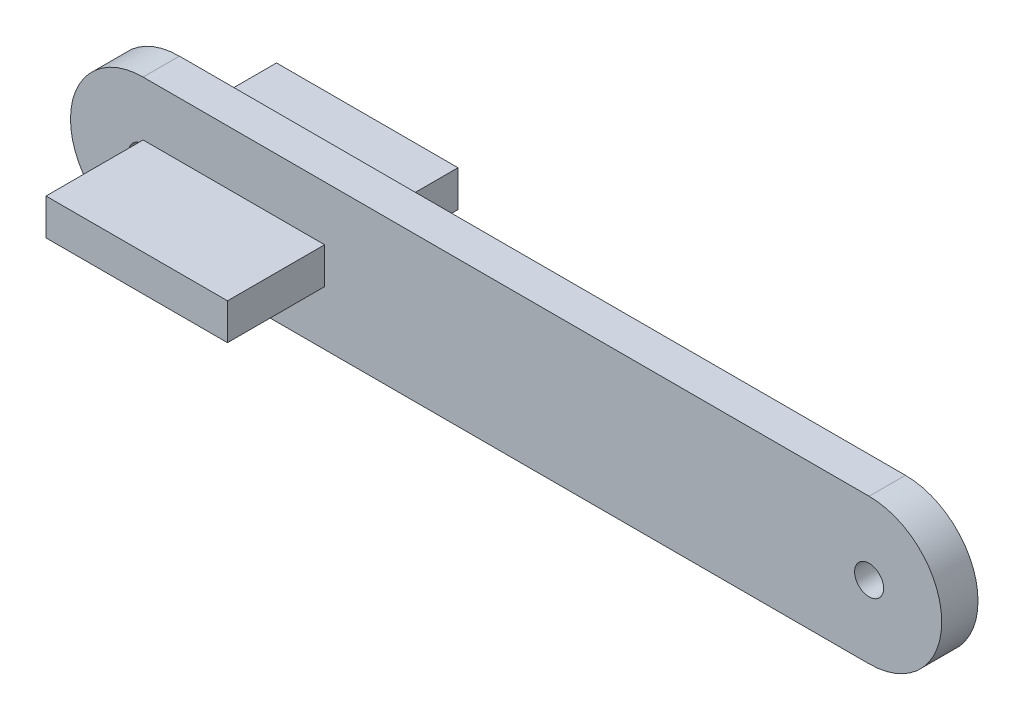
SolidWorks part; units mm, degrees
ref_plane "Front Plane" through (0, 0, 0) normal (0, 0, 1) x (1, 0, 0)
ref_plane "Top Plane" through (0, 0, 0) normal (0, 1, 0) x (1, 0, 0)
ref_plane "Right Plane" through (0, 0, 0) normal (1, 0, 0) x (0, 0, -1)
sketch "Sketch1" plane through (0, 0, 0) normal (0, 0, 1) x (1, 0, 0)
  line L0 (-50, 0) -> (50, 0) construction
  line L1 (-50, 10) -> (50, 10)
  line L2 (-50, -10) -> (50, -10)
  arc A0 (-50, 10) -> (-50, -10) centre (-50, 0) ccw
  arc A1 (50, -10) -> (50, 10) centre (50, 0) ccw
  circle A2 centre (-50, 0) radius 2
  circle A3 centre (50, 0) radius 2
  point P2 (0, 0)
  dimension "D3" = 4
  dimension "D1" = 100
  dimension "D2" = 20
extrude "Boss-Extrude1" add sketch "Sketch1" along normal blind 2.5 and the other way blind 2.5
sketch "Sketch2" plane through (0, 0, 0) normal (1, 0, 0) x (0, 0, -1)
  line L1 (-15.875, -2.5) -> (15.875, -2.5)
  line L2 (-15.875, -2.5) -> (-15.875, 2.5)
  line L3 (-15.875, 2.5) -> (15.875, 2.5)
  line L4 (15.875, -2.5) -> (15.875, 2.5)
  line L5 (-15.875, -2.5) -> (15.875, 2.5) construction
  line L6 (-15.875, 2.5) -> (15.875, -2.5) construction
  point P0 (0, 0)
  dimension "D1" = 5
  dimension "D2" = 31.75
extrude "Boss-Extrude2" add sketch "Sketch2" along normal blind 25 from offset 50 offset against normal yes
